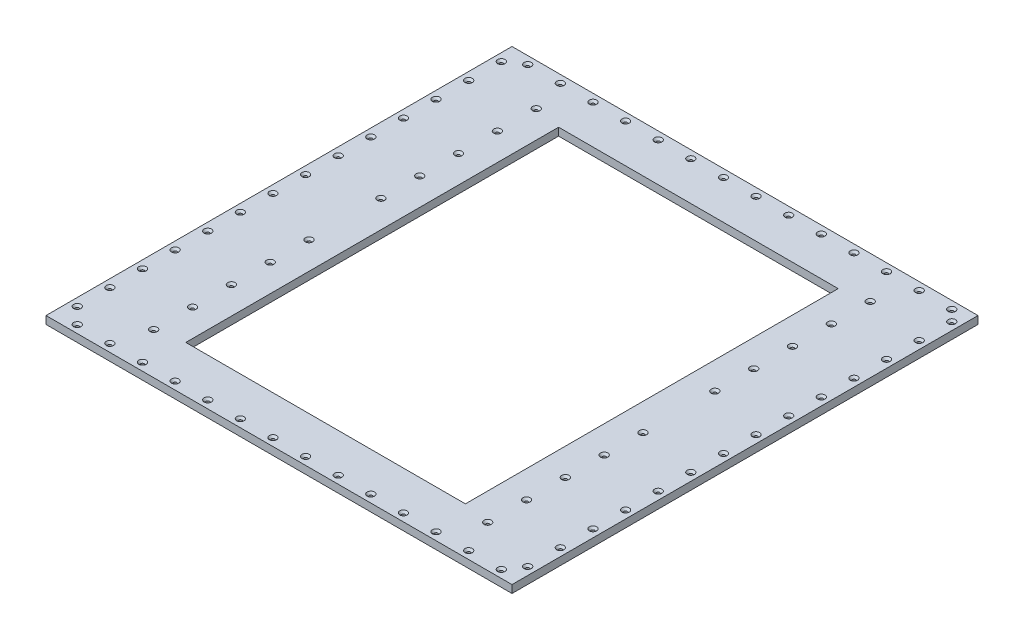
SolidWorks part; units mm, degrees
ref_plane "Płaszczyzna przednia" through (0, 0, 0) normal (0, 0, 1) x (1, 0, 0)
ref_plane "Płaszczyzna górna" through (0, 0, 0) normal (0, 1, 0) x (1, 0, 0)
ref_plane "Płaszczyzna prawa" through (0, 0, 0) normal (1, 0, 0) x (0, 0, -1)
sketch "Sketch1" plane through (0, 0, 0) normal (0, 1, 0) x (1, 0, 0)
  line L1 (0, 0) -> (600, 0)
  line L2 (0, 0) -> (0, 600)
  line L3 (0, 600) -> (600, 600)
  line L4 (600, 0) -> (600, 600)
  line L5 (0, 0) -> (600, 600) construction
  line L6 (0, 600) -> (600, 0) construction
  point P4 (300, 300)
  dimension "D1" = 600
  dimension "D2" = 600
extrude "Boss-Extrude1" add sketch "Sketch1" along normal blind 10
hole_wizard "CSK for M4 Flat Head Machine Screw1" positions "Sketch2" profile "Sketch3" countersink size "M4" standard "ANSI Metric" end condition through all
sketch "Sketch2" plane through (0, 10, 0) normal (0, 1, 0) x (1, 0, 0)
  line L0 (0, 0) -> (600, 0) construction
  line L1 (0, 600) -> (0, 0) construction
  line L2 (600, 0) -> (600, 600) construction
  point P0 (30.25, 10)
  point P14 (72.25, 10)
  point P15 (114.25, 10)
  point P16 (156.25, 10)
  point P17 (198.25, 10)
  point P18 (240.25, 10)
  point P19 (282.25, 10)
  point P20 (324.25, 10)
  point P21 (366.25, 10)
  point P22 (408.25, 10)
  point P23 (450.25, 10)
  point P24 (492.25, 10)
  point P25 (534.25, 10)
  point P26 (576.25, 10)
  point P27 (72.25, 590)
  point P28 (114.25, 590)
  point P29 (156.25, 590)
  point P30 (198.25, 590)
  point P31 (240.25, 590)
  point P32 (282.25, 590)
  point P33 (324.25, 590)
  point P34 (366.25, 590)
  point P35 (408.25, 590)
  point P36 (450.25, 590)
  point P37 (492.25, 590)
  point P38 (534.25, 590)
  point P39 (576.25, 590)
  point P40 (30.25, 590)
  point P42 (590, 30.25)
  point P59 (10, 30.25)
  point P60 (10, 72.25)
  point P61 (10, 114.25)
  point P62 (10, 156.25)
  point P63 (10, 198.25)
  point P64 (10, 240.25)
  point P65 (10, 282.25)
  point P66 (10, 324.25)
  point P67 (10, 366.25)
  point P68 (10, 408.25)
  point P69 (10, 450.25)
  point P70 (10, 492.25)
  point P71 (10, 534.25)
  point P72 (10, 576.25)
  point P73 (590, 72.25)
  point P74 (590, 114.25)
  point P75 (590, 156.25)
  point P76 (590, 198.25)
  point P77 (590, 240.25)
  point P78 (590, 282.25)
  point P79 (590, 324.25)
  point P80 (590, 366.25)
  point P81 (590, 408.25)
  point P82 (590, 450.25)
  point P83 (590, 492.25)
  point P84 (590, 534.25)
  point P85 (590, 576.25)
  dimension "D1" = 10
  dimension "D2" = 30.25
  dimension "D5" = 10
  dimension "D6" = 30.25
  dimension "D3" = 14
  dimension "D4" = 2
  dimension "D7" = 2
  dimension "D8" = 14
sketch "Sketch3" plane through (30.25, 10, -10) normal (1, 0, 0) x (0, 0, 1)
  line L0 (0, 0) -> (0, 10)
  line L1 (0, 10) -> (2.15, 10)
  line L2 (2.15, 10) -> (2.15, 2.55)
  line L3 (2.15, 2.55) -> (4.7, 0)
  line L5 (4.7, 0) -> (0, 0)
  line L6 (-2.15, 2.55) -> (-4.7, 0) construction
  line L11 (0, -6.35) -> (0, 107.95) construction
  dimension "Thru Hole Dia." = 4.3
  dimension "Thru Hole Depth" = 10
  dimension "Near C'Sink Dia." = 9.4
  dimension "Near C'Sink Angle" = 90
hole_wizard "CSK for M4 Flat Head Machine Screw2" positions "Sketch4" profile "Sketch5" countersink size "M4" standard "ANSI Metric" end condition through all
sketch "Sketch4" plane through (0, 10, 0) normal (0, 1, 0) x (1, 0, 0)
  line L0 (0, 0) -> (600, 0) construction
  line L1 (0, 600) -> (0, 0) construction
  line L2 (600, 600) -> (0, 600) construction
  point P0 (84.93, 53.75)
  point P14 (514.93, 53.75)
  point P15 (514.93, 103.75)
  point P16 (514.93, 153.75)
  point P17 (514.93, 203.75)
  point P18 (514.93, 253.75)
  point P19 (84.93, 103.75)
  point P20 (84.93, 153.75)
  point P21 (84.93, 203.75)
  point P22 (84.93, 253.75)
  point P23 (84.93, 546.25)
  point P36 (514.93, 546.25)
  point P37 (514.93, 496.25)
  point P38 (514.93, 446.25)
  point P39 (514.93, 396.25)
  point P40 (514.93, 346.25)
  point P41 (84.93, 496.25)
  point P42 (84.93, 446.25)
  point P43 (84.93, 396.25)
  point P44 (84.93, 346.25)
  dimension "D1" = 53.75
  dimension "D2" = 84.93
  dimension "D5" = 53.75
  dimension "D6" = 84.93
  dimension "D3" = 2
  dimension "D4" = 5
  dimension "D7" = 2
  dimension "D8" = 5
sketch "Sketch5" plane through (84.93, 10, -53.75) normal (1, 0, 0) x (0, 0, 1)
  line L0 (0, 0) -> (0, 10)
  line L1 (0, 10) -> (2.15, 10)
  line L2 (2.15, 10) -> (2.15, 2.55)
  line L3 (2.15, 2.55) -> (4.7, 0)
  line L5 (4.7, 0) -> (0, 0)
  line L6 (-2.15, 2.55) -> (-4.7, 0) construction
  line L11 (0, -6.35) -> (0, 107.95) construction
  dimension "Thru Hole Dia." = 4.3
  dimension "Thru Hole Depth" = 10
  dimension "Near C'Sink Dia." = 9.4
  dimension "Near C'Sink Angle" = 90
sketch "Sketch6" plane through (0, 10, 0) normal (0, 1, 0) x (1, 0, 0)
  line L0 (0, 600) -> (0, 0) construction
  line L1 (120, 540) -> (480, 540)
  line L2 (120, 540) -> (120, 60)
  line L3 (120, 60) -> (480, 60)
  line L4 (480, 540) -> (480, 60)
  line L5 (120, 540) -> (480, 60) construction
  line L6 (120, 60) -> (480, 540) construction
  line L7 (600, 0) -> (600, 600) construction
  line L8 (0, 0) -> (600, 0) construction
  line L9 (600, 600) -> (0, 600) construction
  point P4 (300, 300)
  dimension "D1" = 120
  dimension "D2" = 120
  dimension "D3" = 60
  dimension "D4" = 60
extrude "Cut-Extrude1" cut sketch "Sketch6" against normal blind 10
sketch "Sketch7" plane through (0, 0, 0) normal (0, -1, 0) x (1, 0, 0)
  line L0 (600, -600) -> (0, -600) construction
  line L1 (72, -550) -> (58, -550)
  line L2 (72, -550) -> (72, -50)
  line L3 (72, -50) -> (58, -50)
  line L4 (58, -550) -> (58, -50)
  line L5 (72, -550) -> (58, -50) construction
  line L6 (72, -50) -> (58, -550) construction
  line L7 (0, -600) -> (0, 0) construction
  line L8 (112, -550) -> (112, -50)
  line L9 (112, -550) -> (98, -550)
  line L10 (98, -550) -> (98, -50)
  line L11 (112, -50) -> (98, -50)
  line L12 (542, -550) -> (542, -50)
  line L13 (542, -50) -> (528, -50)
  line L14 (528, -550) -> (528, -50)
  line L15 (542, -550) -> (528, -550)
  line L16 (502, -50) -> (488, -550) construction
  line L17 (502, -550) -> (502, -50)
  line L18 (502, -550) -> (488, -550)
  line L19 (488, -550) -> (488, -50)
  line L20 (502, -50) -> (488, -50)
  point P4 (65, -300)
  dimension "D1" = 50
  dimension "D2" = 500
  dimension "D3" = 14
  dimension "D4" = 72
  dimension "D5" = 2
  dimension "D6" = 2
extrude "Cut-Extrude2" cut sketch "Sketch7" against normal blind 2
chamfer "Chamfer1" distance 2 angle 45 16 edges at (65, 2, -550) (58, 2, -300) (65, 2, -50) (72, 2, -300) (98, 2, -300) (105, 2, -50) (112, 2, -300) (105, 2, -550) (488, 2, -300) (495, 2, -50) (502, 2, -300) (495, 2, -550) (528, 2, -300) (535, 2, -50) (542, 2, -300) (535, 2, -550)
